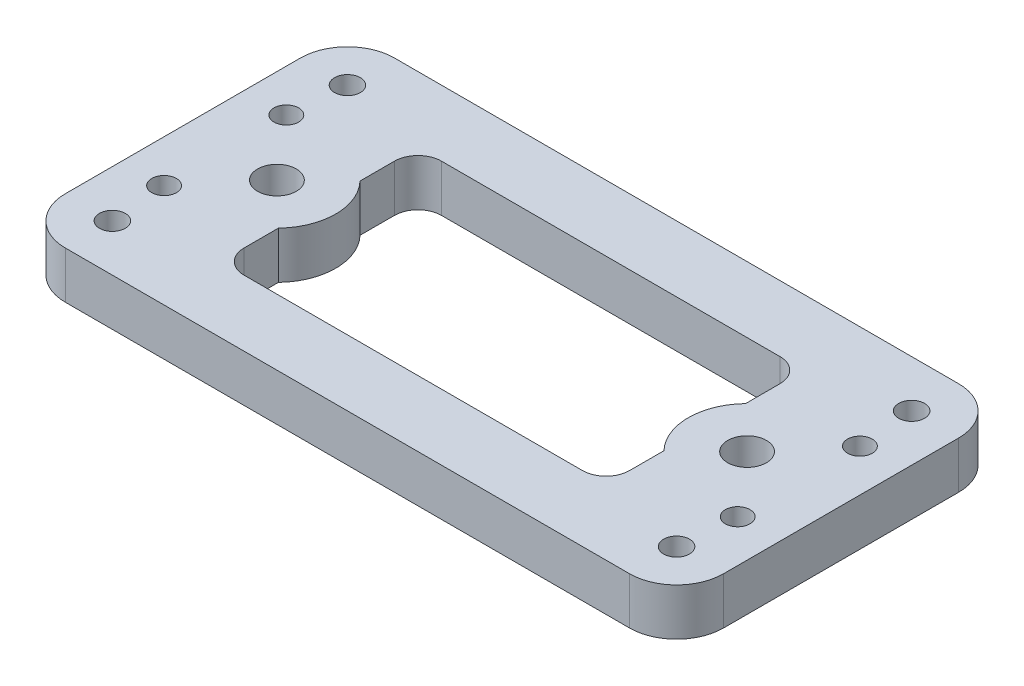
SolidWorks part; units mm, degrees
material "Pine"
ref_plane "Front Plane" through (0, 0, 0) normal (0, 0, 1) x (1, 0, 0)
ref_plane "Top Plane" through (0, 0, 0) normal (0, 1, 0) x (1, 0, 0)
ref_plane "Right Plane" through (0, 0, 0) normal (1, 0, 0) x (0, 0, -1)
sketch "Sketch1" plane through (0, 0, 0) normal (0, 1, 0) x (1, 0, 0)
  line L1 (-41, 21) -> (41, 21)
  line L2 (-41, 21) -> (-41, -21)
  line L3 (-41, -21) -> (41, -21)
  line L4 (41, 21) -> (41, -21)
  line L5 (-41, 21) -> (41, -21) construction
  line L6 (-41, -21) -> (41, 21) construction
  line L7 (-70, 35) -> (70, 35)
  line L8 (-70, 35) -> (-70, -35)
  line L9 (-70, -35) -> (70, -35)
  line L10 (70, 35) -> (70, -35)
  line L11 (-70, 35) -> (70, -35) construction
  line L12 (-70, -35) -> (70, 35) construction
  point P0 (0, 0)
  point P6 (0, 0)
  dimension "D1" = 29
  dimension "D2" = 14
  dimension "D3" = 140
  dimension "D4" = 70
extrude "Boss-Extrude1" add sketch "Sketch1" along normal blind 10
fillet "Fillet1" radius 10 4 edges at (70, 5, 35) (70, 5, -35) (-70, 5, -35) (-70, 5, 35)
sketch "Sketch2" plane through (0, 10, 0) normal (0, 1, 0) x (1, 0, 0)
  line L0 (-60, -35) -> (60, -35) construction
  line L1 (-70, 25) -> (-70, -25) construction
  line L2 (0, 0) -> (0, 48.6702) construction
  line L3 (0, 0) -> (23.6821, 0) construction
  circle A0 centre (-60, -25) radius 2.75
  circle A1 centre (-60, 25) radius 2.75
  circle A2 centre (60, -25) radius 2.75
  circle A3 centre (60, 25) radius 2.75
  dimension "D1" = 5.5
  dimension "D2" = 10
  dimension "D3" = 10
extrude "Cut-Extrude1" cut sketch "Sketch2" against normal through all
sketch "Sketch3" plane through (0, 10, 0) normal (0, 1, 0) x (1, 0, 0)
  line L0 (0, 0) -> (0, 59.0273) construction
  line L1 (-70, 25) -> (-70, -25) construction
  circle A0 centre (-50, 0) radius 4.125
  circle A1 centre (50, 0) radius 4.125
  dimension "D1" = 8.25
  dimension "D2" = 20
extrude "Cut-Extrude2" cut sketch "Sketch3" against normal through all
sketch "Sketch4" plane through (0, 10, 0) normal (0, 1, 0) x (1, 0, 0)
  line L0 (0, 0) -> (0, 50.6676) construction
  line L1 (-41, 21) -> (-41, -21) construction
  line L2 (-41, 8.6747) -> (-41, -8.6747)
  line L3 (41, 8.6747) -> (41, -8.6747)
  arc A0 (-41, 8.6747) -> (-41, -8.6747) centre (-50, 0) cw
  arc A1 (41, 8.6747) -> (41, -8.6747) centre (50, 0) ccw
  dimension "D1" = 12.5
extrude "Boss-Extrude2" add sketch "Sketch4" against normal up to vertex (10 mm away) up to point (-60, 0, 35)
fillet "Fillet2" radius 5 4 edges at (41, 5, 21) (41, 5, -21) (-41, 5, 21) (-41, 5, -21)
sketch "Sketch6" plane through (0, 10, 0) normal (0, 1, 0) x (1, 0, 0)
  circle A0 centre (-61, 13) radius 2.625
  circle A1 centre (-61, -13) radius 2.625
  circle A2 centre (61, 13) radius 2.625
  circle A3 centre (61, -13) radius 2.625
  circle A4 centre (-61, -13) radius 2.625 construction
  circle A5 centre (-61, 13) radius 2.625 construction
  circle A6 centre (61, -13) radius 2.625 construction
  circle A7 centre (61, 13) radius 2.625 construction
extrude "Cut-Extrude3" cut sketch "Sketch6" against normal through all
